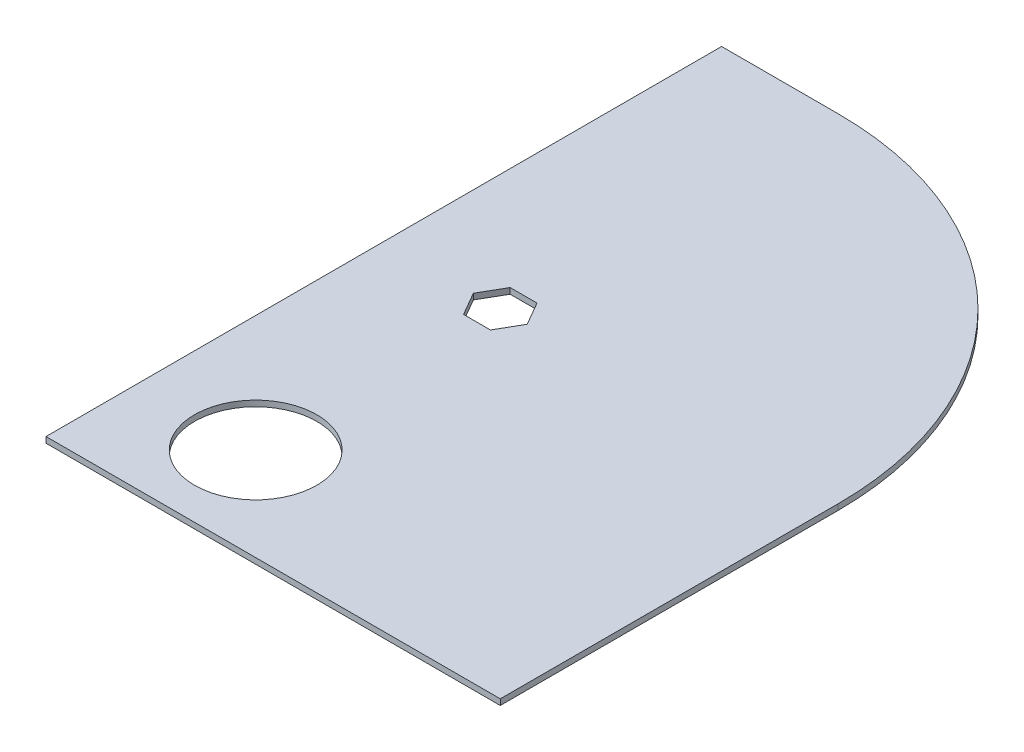
SolidWorks part; units mm, degrees
material "Acrylic (Medium-high impact)"
ref_plane "Front Plane" through (0, 0, 0) normal (0, 0, 1) x (1, 0, 0)
ref_plane "Top Plane" through (0, 0, 0) normal (0, 1, 0) x (1, 0, 0)
ref_plane "Right Plane" through (0, 0, 0) normal (1, 0, 0) x (0, 0, -1)
sketch "Sketch1" plane through (0, 0, 0) normal (0, 1, 0) x (1, 0, 0)
  line L0 (0, 145) -> (145, 145) construction
  line L1 (0, 0) -> (-50, 0)
  line L2 (0, 0) -> (0, 290) construction
  line L3 (0, 290) -> (-50, 290)
  line L4 (-50, 0) -> (-50, 290)
  line L5 (145, 145) -> (145, 0)
  line L6 (145, 0) -> (0, 0)
  arc A0 (0, 290) -> (145, 145) centre (0, 145) cw
  circle A1 centre (0, 250) radius 20 construction
  circle A2 centre (0, 250) radius 25 construction
  point P7 (0, 145)
  point P11 (0, 270)
  point P12 (-20, 250)
  dimension "D2" = 40
  dimension "D5" = 50
  dimension "D1" = 290
  dimension "D3" = 105
  dimension "D4" = 30
sketch "Sketch2" plane through (0, 0, 0) normal (0, 1, 0) x (1, 0, 0)
  line L0 (0, 0) -> (0, 290) construction
  line L1 (-27.5, 250) -> (27.5, 250) construction
  line L2 (-27.5, 250) -> (-27.5, 217.5)
  line L3 (-27.5, 217.5) -> (27.5, 217.5)
  line L4 (27.5, 250) -> (27.5, 217.5)
  line L5 (-27.5, 250) -> (27.5, 217.5) construction
  line L6 (-27.5, 217.5) -> (27.5, 250) construction
  arc A0 (-27.5, 250) -> (27.5, 250) centre (0, 250) cw
  point P0 (0, 233.75)
  dimension "D1" = 27.5
  dimension "D2" = 32.5
sketch "Sketch3" plane through (0, 0, 0) normal (0, 1, 0) x (1, 0, 0)
  line L0 (0, 0) -> (0, 290) construction
  circle A0 centre (0, 40) radius 26.25
  dimension "D2" = 52.5
  dimension "D1" = 105
extrude "Boss-Extrude2" add sketch "Sketch1" along normal blind 2.5
extrude "Cut-Extrude2" [suppressed] cut sketch "Sketch2" along normal through all
extrude "Cut-Extrude3" cut sketch "Sketch3" along normal through all
sketch "Sketch4" [suppressed] plane through (0, 0, 0) normal (0, 1, 0) x (1, 0, 0)
  line L0 (0, 217.5) -> (0, 209.5) construction
  line L1 (-27.5, 217.5) -> (27.5, 217.5) construction
  line L2 (-12.5, 209.5) -> (12.5, 209.5) construction
  circle A0 centre (12.5, 209.5) radius 1.6
  circle A1 centre (-12.5, 209.5) radius 1.6
  dimension "D2" = 3.2
  dimension "D1" = 8
  dimension "D3" = 25
extrude "Cut-Extrude4" [suppressed] cut sketch "Sketch4" along normal blind 10
sketch "Sketch6" plane through (0, 0, 0) normal (0, 1, 0) x (1, 0, 0)
  line L1 (0, 0) -> (0, 290) construction
  line L2 (5.7735, 135) -> (11.547, 145)
  line L3 (11.547, 145) -> (5.7735, 155)
  line L4 (5.7735, 155) -> (-5.7735, 155)
  line L5 (-5.7735, 155) -> (-11.547, 145)
  line L6 (-11.547, 145) -> (-5.7735, 135)
  line L7 (-5.7735, 135) -> (5.7735, 135)
  arc A0 (145, 145) -> (0, 290) centre (0, 145) ccw construction
  circle A2 centre (0, 145) radius 10 construction
  point P1 (0, 145)
  dimension "D1" = 20
extrude "Cut-Extrude5" cut sketch "Sketch6" along normal through all
